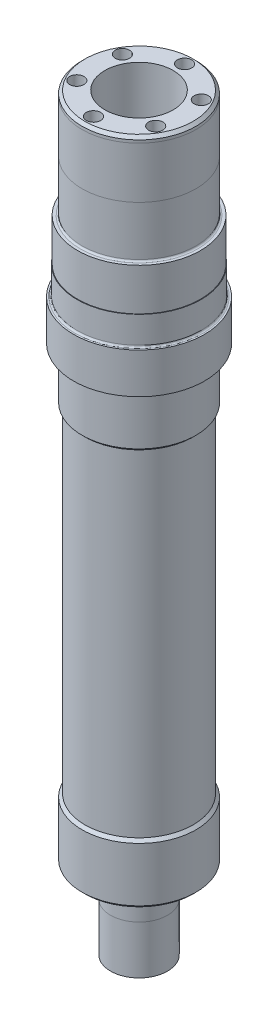
SolidWorks part; units mm, degrees
material "1.4305 (X8CrNiS18-9)"
ref_plane "Front Plane" through (0, 0, 0) normal (0, 0, 1) x (1, 0, 0)
ref_plane "Top Plane" through (0, 0, 0) normal (0, 1, 0) x (1, 0, 0)
ref_plane "Right Plane" through (0, 0, 0) normal (1, 0, 0) x (0, 0, -1)
ref_axis "Wrist" through (0, -55.814, 25) along (0, 1, 0)
sketch "Sketch1" plane through (0, 0, 0) normal (1, 0, 0) x (0, 0, -1)
  line L0 (-35, 83) -> (-15, 83) construction
  line L1 (-35, 65) -> (-15, 65) construction
  line L2 (-35, -32.5) -> (-15, -32.5) construction
  line L3 (-15, 45.5) -> (-35, 45.5) construction
  line L4 (-35, 83) -> (-15, 83) construction
  line L5 (-35, 65) -> (-15, 65) construction
  line L6 (-35, -32.5) -> (-15, -32.5) construction
  line L7 (-15, 45.5) -> (-35, 45.5) construction
  line L8 (-50, 49.5) -> (0, 49.5) construction
  line L9 (-50, 49.5) -> (0, 49.5) construction
  line L10 (-15, 84) -> (-15, 65)
  line L11 (-15, 65) -> (-14.2, 65)
  line L12 (-14.2, 65) -> (-14.2, 57.6)
  line L17 (-14.2, 57.6) -> (-14.1, 57.6)
  line L19 (-19, 83) -> (-19, -23.5)
  line L20 (-15, 45.5) -> (-15, 36.5)
  line L21 (-19, -33.5) -> (-15, -33.5)
  line L22 (-19, 83) -> (-19, 84)
  line L23 (-19, 84) -> (-15, 84)
  line L26 (14, 47) -> (232.9, 47) construction
  line L27 (14, 47) -> (232.9, 47) construction
  line L28 (-19, -33.5) -> (-20, -33.5)
  line L29 (-20, -33.5) -> (-20, -47.5)
  line L30 (-20, -47.5) -> (-25, -47.5)
  line L31 (-25, -47.5) -> (-25, -23.5)
  line L32 (-25, -23.5) -> (-19, -23.5)
  line L33 (-19, -23.5) -> (-19, -32.5) construction
  line L34 (-19, -32.5) -> (-19, -33.5) construction
  line L35 (-25, -55.814) -> (-25, 57.5977) construction
  line L36 (-35, -23.5) -> (-15, -23.5) construction
  line L37 (-15, 36.5) -> (-35, 36.5) construction
  line L38 (-35, -23.5) -> (-15, -23.5) construction
  line L39 (-15, 36.5) -> (-35, 36.5) construction
  line L41 (-13.5, 45.5) -> (-15, 45.5)
  line L42 (-13.5, 45.5) -> (-13.5, 52.6)
  line L43 (-13.5, 52.6) -> (-14.1, 52.6)
  line L44 (-14.1, 52.6) -> (-14.1, 57.6)
  line L46 (-15, -23.5) -> (-15, -33.5)
  line L47 (-15, 36.5) -> (-15.5, 36.5)
  line L48 (-15.5, 36.5) -> (-15.5, -23.5)
  line L49 (-15.5, -23.5) -> (-15, -23.5)
  dimension "D1" = 1
  dimension "D2" = 1
  dimension "D3" = 0.1
  dimension "D4" = 7.4
  dimension "D5" = 4
  dimension "D6" = 10
  dimension "D7" = 14
  dimension "D8" = 5
  dimension "D9" = 1.5
  dimension "D10" = 5
  dimension "D11" = 0.5
  dimension "D12" = 0.8
revolve "Revolve1" add sketch "Sketch1" angle 360 about axis through (0, -55.814, 25) along (0, 1, 0)
sketch "Sketch2" plane through (0, 0, 0) normal (1, 0, 0) x (0, 0, -1)
  line L1 (-30, -33.5) -> (-20, -33.5) construction
  line L2 (-19, -36) -> (-13, -36)
  line L4 (-15, -34) -> (-19, -34)
  line L6 (-30, -33.5) -> (-20, -33.5) construction
  line L8 (-19, -34) -> (-19, -36)
  line L9 (-15, -34) -> (-15, -32.5)
  line L10 (-15, -32.5) -> (-13, -32.5)
  line L11 (-13, -32.5) -> (-13, -36)
  line L12 (-35, -33.5) -> (-15, -33.5) construction
  line L13 (-25, -55.814) -> (-25, 57.5977) construction
  dimension "D1" = 2
  dimension "D2" = 2
  dimension "D3" = 6
  dimension "D4" = 0.5
revolve "Revolve2" add sketch "Sketch2" angle 360 about axis through (0, -55.814, 25) along (0, 1, 0)
sketch "Sketch13" plane through (0, 0, 0) normal (1, 0, 0) x (0, 0, -1)
  line L0 (-15, 84) -> (-35, 84) construction
  line L1 (-19, 84) -> (-31, 84) construction
  line L2 (-15, 84) -> (-35, 84) construction
  line L3 (-19, 84) -> (-31, 84) construction
  line L5 (-19, 86.5) -> (-13, 86.5)
  line L6 (-13, 86.5) -> (-13, 83)
  line L7 (-13, 83) -> (-15, 83)
  line L10 (-19, 86.5) -> (-19, 84.5)
  line L11 (-19, 84.5) -> (-15, 84.5)
  line L12 (-15, 84.5) -> (-15, 83)
  line L13 (-15, 65) -> (-15, 84) construction
  dimension "D1" = 0.5
  dimension "D2" = 2
  dimension "D3" = 2
  dimension "D4" = 1
revolve "Revolve4" add sketch "Sketch13" angle 360 about axis through (0, -55.814, 25) along (0, 1, 0)
sketch "Sketch6" plane through (0, -36, 0) normal (0, -1, 0) x (-1, 0, 0)
  line L0 (0, -15) -> (0, -19) construction
  line L1 (0, -25) -> (0, -17) construction
  circle A0 centre (0, -25) radius 6 construction
  circle A1 centre (0, -25) radius 10 construction
  circle A2 centre (0, -25) radius 6 construction
  circle A3 centre (0, -25) radius 10 construction
  point P11 (0, -17)
  point P20 (6.9282, -21)
  point P21 (6.9282, -29)
  point P22 (0, -33)
  point P23 (-6.9282, -29)
  point P24 (-6.9282, -21)
  dimension "D1" = 6
hole_wizard "M3 Clearance Hole1" positions "Sketch6" profile "Sketch4" hole size "M3" standard "DIN" end condition up to next
sketch "Sketch4" plane through (6.9282, -36, 21) normal (1, 0, 0) x (0, 0, -1)
  line L0 (0, 0) -> (0, 120)
  line L1 (0, 120) -> (1.6, 120)
  line L2 (1.6, 120) -> (1.6, 0)
  line L5 (1.6, 0) -> (0, 0)
  line L11 (0, -6.35) -> (0, 107.95) construction
  dimension "Thru Hole Dia." = 3.2
  dimension "Thru Hole Depth" = 120
sketch "Sketch9" plane through (0, -33.5, 0) normal (0, -1, 0) x (-1, 0, 0)
  point P0 (0, -17)
  point P3 (-6.9282, -21)
  point P6 (-6.9282, -29)
  point P9 (6.9282, -21)
  point P12 (6.9282, -29)
  point P15 (0, -33)
hole_wizard "M3 Tapped Hole1" positions "Sketch9" profile "Sketch8" tap size "M3" standard "DIN"
sketch "Sketch8" plane through (0, -33.5, 17) normal (1, 0, 0) x (0, 0, -1)
  line L0 (0, 0) -> (0, 9.2511)
  line L1 (0, 9.2511) -> (1.25, 8.5)
  line L2 (1.25, 8.5) -> (1.25, 0)
  line L5 (1.25, 0) -> (0, 0)
  line L10 (0, 9.2511) -> (-1.25, 8.5) construction
  line L11 (0, -6.35) -> (0, 107.95) construction
  dimension "Tap Drill Dia." = 2.5
  dimension "Tap Drill Depth" = 8.5
  dimension "Drill Angle" = 118
cosmetic thread "Hole Thread1" parameters "D1"=6, "D2"=3
cosmetic thread "Hole Thread2" parameters "D1"=6, "D2"=3
cosmetic thread "Hole Thread3" parameters "D1"=6, "D2"=3
cosmetic thread "Hole Thread4" parameters "D1"=6, "D2"=3
cosmetic thread "Hole Thread5" parameters "D1"=6, "D2"=3
cosmetic thread "Hole Thread6" parameters "D1"=6, "D2"=3
sketch "Sketch16" plane through (0, 86.5, 0) normal (0, 1, 0) x (1, 0, 0)
  line L0 (0, -15) -> (0, -19) construction
  line L1 (0, -25) -> (0, -17) construction
  circle A0 centre (0, -25) radius 10 construction
  circle A2 centre (0, -25) radius 10
  circle A3 centre (0, -25) radius 6
  circle A4 centre (0, -25) radius 6 construction
  point P11 (0, -17)
  point P21 (6.9282, -21)
  point P22 (6.9282, -29)
  point P23 (0, -33)
  point P24 (-6.9282, -29)
  point P25 (-6.9282, -21)
  dimension "D1" = 6
hole_wizard "M3 Clearance Hole2" positions "Sketch16" profile "Sketch15" hole size "M3" standard "DIN" end condition through all
sketch "Sketch15" plane through (-6.9282, 86.5, 21) normal (1, 0, 0) x (0, 0, 1)
  line L0 (0, 0) -> (0, 134)
  line L1 (0, 134) -> (1.6, 134)
  line L2 (1.6, 134) -> (1.6, 0)
  line L5 (1.6, 0) -> (0, 0)
  line L11 (0, -6.35) -> (0, 107.95) construction
  dimension "Thru Hole Dia." = 3.2
  dimension "Thru Hole Depth" = 134
sketch "Sketch19" plane through (0, 84, 0) normal (0, 1, 0) x (1, 0, 0)
  point P0 (-6.9282, -29)
  point P3 (0, -33)
  point P6 (6.9282, -29)
  point P9 (6.9282, -21)
  point P12 (0, -17)
  point P15 (-6.9282, -21)
hole_wizard "M3 Tapped Hole2" positions "Sketch19" profile "Sketch20" tap size "M3" standard "DIN"
sketch "Sketch20" plane through (-6.9282, 84, 29) normal (1, 0, 0) x (0, 0, 1)
  line L0 (0, 0) -> (0, 8.2511)
  line L1 (0, 8.2511) -> (1.25, 7.5)
  line L2 (1.25, 7.5) -> (1.25, 0)
  line L5 (1.25, 0) -> (0, 0)
  line L10 (0, 8.2511) -> (-1.25, 7.5) construction
  line L11 (0, -6.35) -> (0, 107.95) construction
  dimension "Tap Drill Dia." = 2.5
  dimension "Tap Drill Depth" = 7.5
  dimension "Drill Angle" = 118
cosmetic thread "Hole Thread7" parameters "D1"=6, "D2"=3
cosmetic thread "Hole Thread8" parameters "D1"=6, "D2"=3
cosmetic thread "Hole Thread9" parameters "D1"=6, "D2"=3
cosmetic thread "Hole Thread10" parameters "D1"=6, "D2"=3
cosmetic thread "Hole Thread11" parameters "D1"=6, "D2"=3
cosmetic thread "Hole Thread12" parameters "D1"=6, "D2"=3
sketch "Sketch10" plane through (0, 0, 0) normal (1, 0, 0) x (0, 0, -1)
  line L1 (-19, -33.5) -> (-19, -25.5)
  line L2 (-31, -33.5) -> (-19, -33.5) construction
  line L3 (-31, -33.5) -> (-19, -33.5) construction
  line L4 (-19, -25.5) -> (-22, -25.5)
  line L5 (-22, -25.5) -> (-22, -41.5)
  line L6 (-22, -41.5) -> (-19.5, -41.5)
  line L7 (-19.5, -41.5) -> (-19.5, -33.5)
  line L8 (-19.5, -33.5) -> (-19, -33.5)
  dimension "D1" = 0.5
  dimension "D2" = 8
  dimension "D3" = 8
  dimension "D4" = 3
revolve "Revolve3" [suppressed] add sketch "Sketch10" angle 360 about axis through (0, -55.814, 25) along (0, 1, 0)
sketch "Sketch11" plane through (0, 0, 0) normal (1, 0, 0) x (0, 0, -1)
  line L0 (-35, 83) -> (-15, 83) construction
  line L1 (-35, 74) -> (-15, 74) construction
  line L2 (-35, 83) -> (-15, 83)
  line L6 (-35, 74) -> (-15, 74)
split line "Split Line1"
sketch "Sketch12" plane through (0, 0, 0) normal (1, 0, 0) x (0, 0, -1)
  line L0 (-20, -39) -> (-29.899, -39) construction
  line L2 (-20, -39) -> (-29.899, -39)
  line L3 (-29.899, -39) -> (-30, -39)
  line L4 (-30, -33.5) -> (-30, -47.5) construction
split line "Split Line3"
chamfer "Chamfer1" distance 0.5 angle 45 2 edges at (0, 84, 15) (0, -33.5, 15)
fillet "Fillet1" radius 0.3 1 edges at (0, 84.5, 15)
fillet "Fillet2" radius 0.3 1 edges at (0, -34, 15)
fillet "Fillet3" radius 0.4 1 edges at (0, -33.5, 20)
chamfer "Chamfer2" distance 0.5 angle 45 2 edges at (0, 36.5, 15.5) (0, -23.5, 15.5)
fillet "Fillet4" radius 0.3 2 edges at (0, 65, 15) (0, 45.5, 15)
fillet "Fillet5" radius 0.3 1 edges at (0, 52.6, 14.1)
delete or keep bodies "Body-Delete/Keep 1" type delete bodies bodies 110 103
delete or keep bodies "Body-Delete/Keep 2" [suppressed] type delete bodies bodies 113 110
delete or keep bodies "Body-Delete/Keep 3" [suppressed] type delete bodies bodies 103 113
